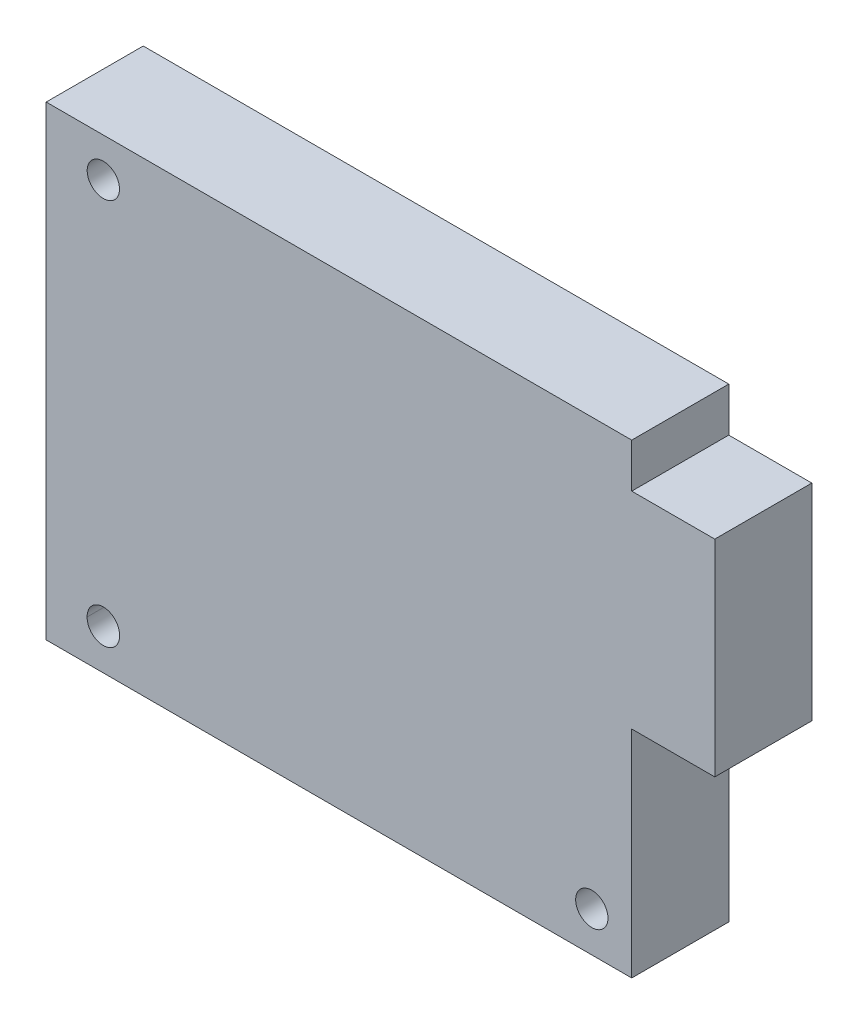
SolidWorks part; units mm, degrees
ref_plane "Plan de face" through (0, 0, 0) normal (0, 0, 1) x (1, 0, 0)
ref_plane "Plan de dessus" through (0, 0, 0) normal (0, 1, 0) x (1, 0, 0)
ref_plane "Plan de droite" through (0, 0, 0) normal (1, 0, 0) x (0, 0, -1)
sketch "Esquisse1" plane through (0, 0, 0) normal (0, 0, 1) x (1, 0, 0)
  line L0 (27.15, 17.5) -> (34.85, 17.5)
  line L1 (-27.15, 21.6) -> (27.15, 21.6)
  line L2 (-27.15, 21.6) -> (-27.15, -21.6)
  line L3 (-27.15, -21.6) -> (27.15, -21.6)
  line L4 (27.15, 21.6) -> (27.15, 17.5)
  line L5 (-27.15, 21.6) -> (27.15, -21.6) construction
  line L6 (-27.15, -21.6) -> (27.15, 21.6) construction
  line L7 (34.85, 17.5) -> (34.85, -1.6)
  line L8 (34.85, -1.6) -> (27.15, -1.6)
  line L9 (27.15, -1.6) -> (27.15, -21.6)
  point P0 (0, 0)
  dimension "D1" = 54.3
  dimension "D2" = 43.2
  dimension "D3" = 19.1
  dimension "D4" = 4.1
  dimension "D5" = 62
extrude "Boss.-Extru.1" add sketch "Esquisse1" along normal blind 9
hole_wizard "Dégagement M3.51" positions "Esquisse2" profile "Esquisse3" hole size "M3.5" standard "Ansi Metric" end condition up to next
sketch "Esquisse2" plane through (0, 0, 9) normal (0, 0, 1) x (1, 0, 0)
  line L0 (27.15, -21.6) -> (27.15, -1.6) construction
  line L1 (-27.15, -21.6) -> (27.15, -21.6) construction
  point P0 (-21.85, 18)
  point P2 (-21.85, -17.9)
  point P4 (-21.85, -17.8)
  point P7 (23.45, -17.9)
  dimension "D1" = 45.3
  dimension "D2" = 35.9
  dimension "D3" = 3.7
  dimension "D4" = 3.7
sketch "Esquisse3" plane through (-21.85, 18, 9) normal (1, 0, 0) x (0, -1, 0)
  line L0 (0, 0) -> (0, 9)
  line L1 (0, 9) -> (1.5, 9)
  line L2 (1.5, 9) -> (1.5, 0)
  line L5 (1.5, 0) -> (0, 0)
  line L11 (0, -6.35) -> (0, 107.95) construction
  dimension "Diamètre du perçage jusqu'au prochain" = 3
  dimension "Profondeur du perçage jusqu'au prochain" = 9
